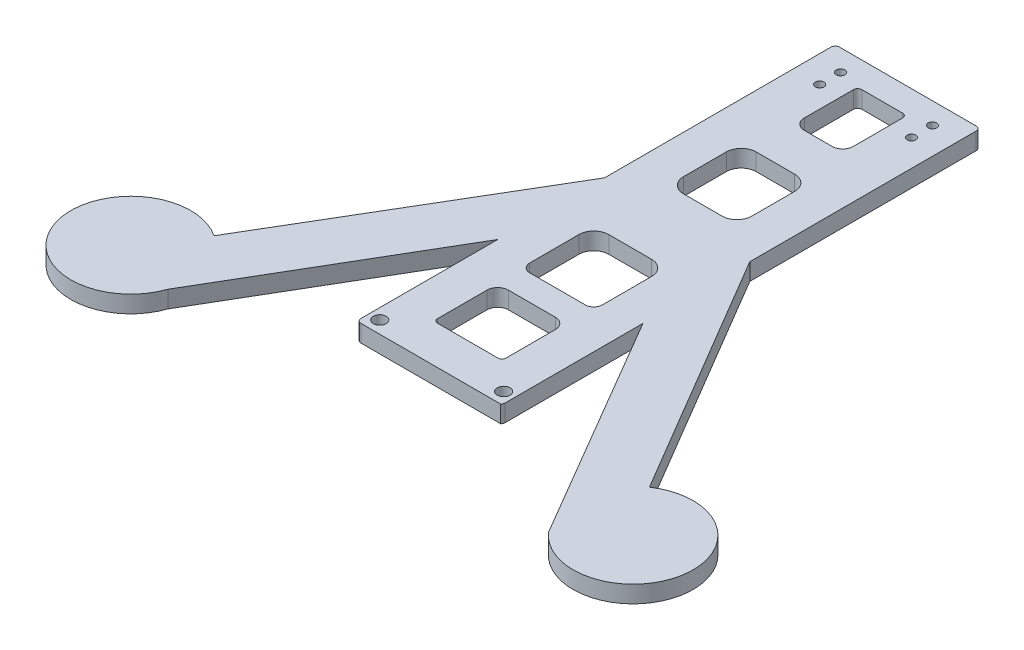
SolidWorks part; units mm, degrees
ref_plane "Front Plane" through (0, 0, 0) normal (0, 0, 1) x (1, 0, 0)
ref_plane "Top Plane" through (0, 0, 0) normal (0, 1, 0) x (1, 0, 0)
ref_plane "Right Plane" through (0, 0, 0) normal (1, 0, 0) x (0, 0, -1)
sketch "Frame Sketch" plane through (0, 0, 0) normal (0, 1, 0) x (1, 0, 0)
  line L0 (2.2808, 0.1404) -> (2.2808, 126.6085) construction
  line L6 (-48.6747, 0) -> (67.0859, 0) construction
  line L11 (2.2808, 0.1404) -> (2.2808, -105.8001) construction
  line L23 (-14.7192, 56.1404) -> (18.2808, 56.1404)
  line L24 (-14.7192, 56.1404) -> (-14.7192, -54.8596)
  line L25 (-13.7192, -55.8596) -> (19.2808, -55.8596)
  line L26 (19.2808, 55.1404) -> (19.2808, -55.8596)
  line L27 (-14.7192, 56.1404) -> (19.2808, -55.8596) construction
  line L28 (-14.7192, -55.8596) -> (19.2808, 56.1404) construction
  line L29 (-14.7192, 2.1404) -> (-48.6747, -55.2899)
  line L30 (-14.7192, -22.8596) -> (-14.7192, 2.1404)
  line L31 (-14.7192, -22.8596) -> (-46.0248, -76.2899)
  line L32 (-48.6747, -55.2899) -> (-46.0248, -76.2899)
  line L33 (19.2808, -22.8596) -> (19.2808, 2.1404)
  line L34 (19.2808, -22.8596) -> (50.5864, -76.2899)
  line L37 (53.2362, -55.2899) -> (50.5864, -76.2899)
  line L38 (19.2808, 2.1404) -> (53.2362, -55.2899)
  line L44 (-4.8596, -46.8596) -> (9.4212, -46.8596)
  line L45 (-5.7192, -46) -> (-5.7192, -34.3596)
  line L46 (-3.2192, -31.8596) -> (7.7808, -31.8596)
  line L47 (10.2808, -46) -> (10.2808, -34.3596)
  line L48 (-5.7192, -46.8596) -> (10.2808, -31.8596) construction
  line L49 (-5.7192, -31.8596) -> (10.2808, -46.8596) construction
  line L50 (8.7808, -25.8596) -> (-4.2192, -25.8596)
  line L51 (10.7808, -23.8596) -> (10.7808, -12.3596)
  line L52 (7.2808, -8.8596) -> (-2.7192, -8.8596)
  line L53 (-6.2192, -23.8596) -> (-6.2192, -12.3596)
  line L54 (10.7808, -25.8596) -> (-6.2192, -8.8596) construction
  line L55 (10.7808, -8.8596) -> (-6.2192, -25.8596) construction
  line L56 (-2.2192, 8.1404) -> (6.7808, 8.1404)
  line L57 (-5.7192, 11.6404) -> (-5.7192, 21.6404)
  line L58 (-2.2192, 25.1404) -> (6.7808, 25.1404)
  line L59 (10.2808, 11.6404) -> (10.2808, 21.6404)
  line L60 (-5.7192, 8.1404) -> (10.2808, 25.1404) construction
  line L61 (-5.7192, 25.1404) -> (10.2808, 8.1404) construction
  line L62 (-0.9692, 35.1404) -> (5.5308, 35.1404)
  line L63 (-3.4692, 37.6404) -> (-3.4692, 49.1404)
  line L64 (-2.4692, 50.1404) -> (7.0308, 50.1404)
  line L65 (8.0308, 37.6404) -> (8.0308, 49.1404)
  line L66 (-3.4692, 35.1404) -> (8.0308, 50.1404) construction
  line L67 (-3.4692, 50.1404) -> (8.0308, 35.1404) construction
  circle A5 centre (-56.5031, -66.9449) radius 14.04
  circle A6 centre (61.0647, -66.9449) radius 14.04
  arc A8 (19.2808, 55.1404) -> (18.2808, 56.1404) centre (18.2808, 55.1404) ccw
  arc A9 (19.2808, -55.1404) -> (18.2808, -56.1404) centre (18.2808, -55.1404) cw
  arc A10 (-14.7192, 55.1404) -> (-13.7192, 56.1404) centre (-13.7192, 55.1404) cw
  arc A11 (-13.7192, -55.8596) -> (-14.7192, -54.8596) centre (-13.7192, -54.8596) cw
  circle A12 centre (-12.2192, -52.9596) radius 1.5
  circle A13 centre (16.7808, -52.9596) radius 1.5
  arc A14 (10.2808, -46) -> (9.4212, -46.8596) centre (9.4212, -46) cw
  arc A15 (-4.8596, -46.8596) -> (-5.7192, -46) centre (-4.8596, -46) cw
  arc A16 (-5.7192, -34.3596) -> (-3.2192, -31.8596) centre (-3.2192, -34.3596) cw
  arc A17 (7.7808, -31.8596) -> (10.2808, -34.3596) centre (7.7808, -34.3596) cw
  arc A18 (10.7808, -23.8596) -> (8.7808, -25.8596) centre (8.7808, -23.8596) cw
  arc A19 (-6.2192, -23.8596) -> (-4.2192, -25.8596) centre (-4.2192, -23.8596) ccw
  arc A20 (10.7808, -12.3596) -> (7.2808, -8.8596) centre (7.2808, -12.3596) ccw
  arc A21 (-2.7192, -8.8596) -> (-6.2192, -12.3596) centre (-2.7192, -12.3596) ccw
  arc A22 (-2.2192, 8.1404) -> (-5.7192, 11.6404) centre (-2.2192, 11.6404) cw
  arc A23 (10.2808, 11.6404) -> (6.7808, 8.1404) centre (6.7808, 11.6404) cw
  arc A24 (-2.2192, 25.1404) -> (-5.7192, 21.6404) centre (-2.2192, 21.6404) ccw
  arc A25 (10.2808, 21.6404) -> (6.7808, 25.1404) centre (6.7808, 21.6404) ccw
  arc A26 (-0.9692, 35.1404) -> (-3.4692, 37.6404) centre (-0.9692, 37.6404) cw
  arc A27 (8.0308, 37.6404) -> (5.5308, 35.1404) centre (5.5308, 37.6404) cw
  arc A28 (-2.4692, 50.1404) -> (-3.4692, 49.1404) centre (-2.4692, 49.1404) ccw
  arc A29 (8.0308, 49.1404) -> (7.0308, 50.1404) centre (7.0308, 49.1404) ccw
  circle A30 centre (13.0308, 51.1404) radius 1
  circle A31 centre (13.0308, 46.2404) radius 1
  circle A32 centre (-8.4692, 51.1404) radius 1
  circle A33 centre (-8.4692, 46.2404) radius 1
  point P0 (0, 0)
  point P6 (0, 0)
  point P52 (2.2808, -39.3596)
  point P69 (2.2808, -17.3596)
  point P86 (2.2808, 16.6404)
  point P103 (2.2808, 42.6404)
  dimension "D6" = 1
  dimension "D7" = 2.9
  dimension "D8" = 2.5
  dimension "D5" = 17
  dimension "D11" = 9
  dimension "D12" = 9
  dimension "D13" = 10
  dimension "D14" = 33
  dimension "D30" = 5
  dimension "D31" = 5
  dimension "D32" = 4.9
  dimension "D33" = 6
  dimension "D34" = 5
  dimension "D3" = 112
  dimension "D4" = 34
  dimension "D9" = 15
  dimension "D10" = 16
  dimension "D15" = 17
  dimension "D16" = 6
  dimension "D21" = 17
  dimension "D22" = 16
  dimension "D27" = 17
  dimension "D28" = 15
  dimension "D29" = 11.5
extrude "Frame Bottom Plate" add sketch "Frame Sketch" along normal blind 4 contours L26 L23 L24 L25 | L37 A6 | L34 L37 L38 L33 | L29 L32 L31 L30 | A5 region at (2.2817, 0, -1.1802) region at (62.4938, 0, 67.1253)
